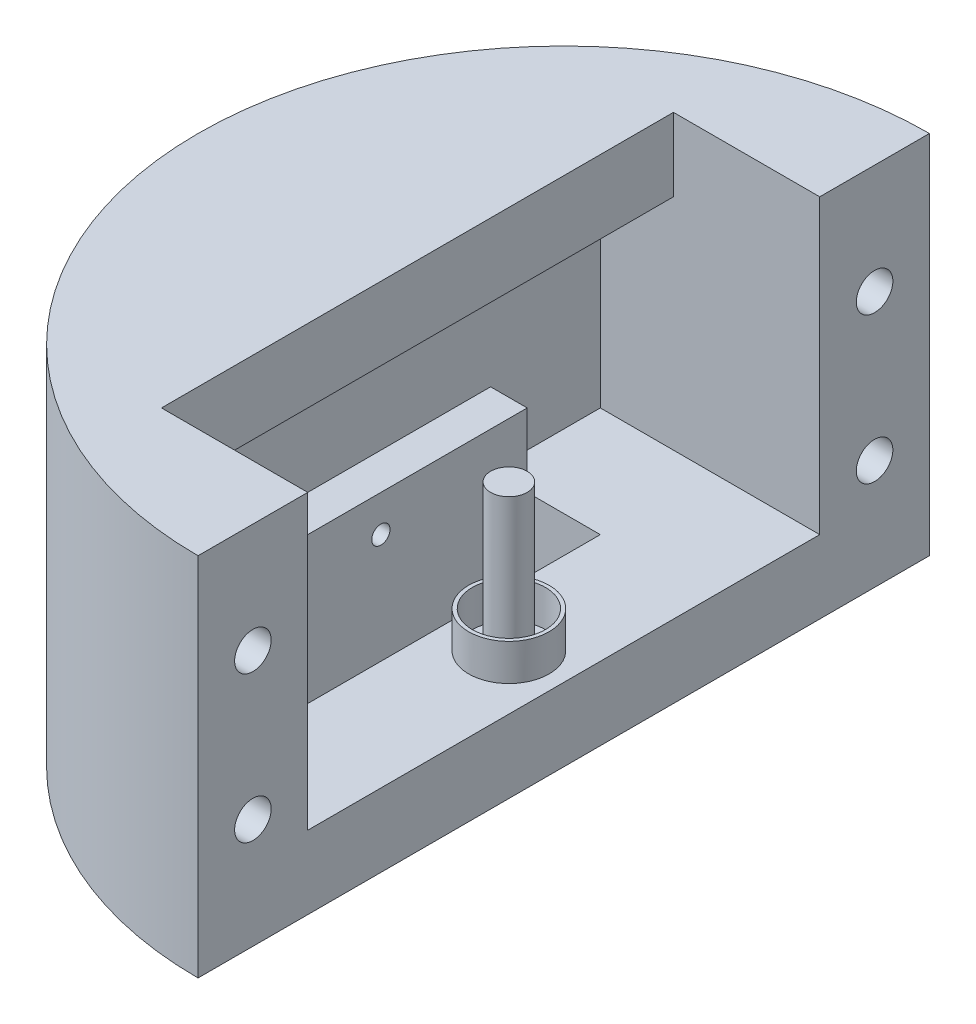
SolidWorks part; units mm, degrees
material "PP Kopolimer"
ref_plane "Front Plane" through (0, 0, 0) normal (0, 0, 1) x (1, 0, 0)
ref_plane "Top Plane" through (0, 0, 0) normal (0, 1, 0) x (1, 0, 0)
ref_plane "Right Plane" through (0, 0, 0) normal (1, 0, 0) x (0, 0, -1)
sketch "Szkic1" plane through (0, 0, 0) normal (0, 1, 0) x (1, 0, 0)
  line L1 (-2.5, -5) -> (2.5, -5)
  line L2 (-2.5, -5) -> (-2.5, 5)
  line L3 (-2.5, 5) -> (2.5, 5)
  line L4 (2.5, -5) -> (2.5, 5)
  line L5 (-2.5, -5) -> (2.5, 5) construction
  line L6 (-2.5, 5) -> (2.5, -5) construction
  point P0 (0, 0)
extrude "Dodanie-wyciągnięcie1" add sketch "Szkic1" along normal blind 1
sketch "Szkic2" plane through (0, 1, 0) normal (0, 1, 0) x (1, 0, 0)
  line L0 (2.5, -5) -> (2.5, 5) construction
  line L1 (-2.5, 5) -> (2.5, 5)
  line L10 (-2.5, 5) -> (-2.5, -5)
  line L15 (-2.5, -5) -> (2.5, -5)
  line L16 (2.5, 3.5) -> (2.5, 5)
  line L17 (-0.5, 3.5) -> (-0.5, -3.5)
  line L18 (2.5, -3.5) -> (2.5, -5)
  line L19 (2.5, 3.5) -> (-0.5, 3.5)
  line L20 (2.5, -3.5) -> (-0.5, -3.5)
extrude "Dodanie-wyciągnięcie4" add sketch "Szkic2" along normal blind 4 contours L17 L20 L18 L15 L10 L1 L16 L19
fillet "Zaokrąglenie2" radius 5 2 edges at (-2.5, 2.5, -5) (-2.5, 2.5, 5)
sketch "Szkic3" plane through (0, 1, 0) normal (0, 1, 0) x (1, 0, 0)
  line L0 (-0.5, 0) -> (0, 0) construction
  line L1 (-0.5, 3.5) -> (-0.5, -3.5) construction
  line L2 (0, 0) -> (0, 2) construction
  line L4 (0, 2) -> (1, 2)
  line L5 (0, 2) -> (0, -2)
  line L6 (0, -2) -> (1, -2)
  line L7 (1, 2) -> (1, -2)
extrude "Wytnij-wyciągnięcie1" cut sketch "Szkic3" against normal blind 4
sketch "Szkic4" plane through (0, 1, 0) normal (0, 1, 0) x (1, 0, 0)
  line L0 (-0.5, 3.5) -> (-0.5, -3.5) construction
  line L1 (0, 2) -> (-0.5, 2)
  line L2 (0, 2) -> (0, -2)
  line L3 (0, -2) -> (-0.5, -2)
  line L4 (-0.5, 2) -> (-0.5, -2)
extrude "Dodanie-wyciągnięcie5" add sketch "Szkic4" along normal blind 1
sketch "Szkic5" plane through (0, 1, 0) normal (0, 1, 0) x (1, 0, 0)
  line L0 (1, 0) -> (2.5, 0) construction
  line L1 (1, -2) -> (1, 2) construction
  line L2 (2.5, -3.5) -> (2.5, 3.5) construction
  circle A0 centre (1.75, 0) radius 0.25
extrude "Dodanie-wyciągnięcie6" add sketch "Szkic5" along normal blind 2
sketch "Szkic6" plane through (0, 1, 0) normal (0, 1, 0) x (1, 0, 0)
  circle A0 centre (1.75, 0) radius 0.5
  circle A1 centre (1.75, 0) radius 0.55
extrude "Dodanie-wyciągnięcie7" add sketch "Szkic6" along normal blind 0.5
sketch "Szkic7" plane through (-0.5, 0, 0) normal (1, 0, 0) x (0, 0, -1)
  line L0 (-3.5, 5) -> (-3.5, 1) construction
  line L1 (3.5, 5) -> (-3.5, 5)
  line L2 (3.5, 5) -> (3.5, 4)
  line L3 (3.5, 4) -> (-3.5, 4)
  line L4 (-3.5, 5) -> (-3.5, 4)
extrude "Dodanie-wyciągnięcie8" add sketch "Szkic7" along normal blind 1
sketch "Szkic11" plane through (2.5, 0, 0) normal (1, 0, 0) x (0, 0, -1)
  line L0 (-4.25, 5) -> (-4.25, 3.5031)
  line L1 (-3.5, 5) -> (-5, 5) construction
  line L2 (-4.25, 3.5031) -> (-4.25, 1.5031)
  line L3 (4.25, 5) -> (4.25, 3.5031) construction
  line L4 (3.5, 5) -> (5, 5) construction
  line L5 (4.25, 3.5031) -> (4.25, 1.5031) construction
  circle A0 centre (-4.25, 3.5031) radius 0.25
  circle A1 centre (-4.25, 1.5031) radius 0.25
  circle A2 centre (4.25, 3.5031) radius 0.25
  circle A3 centre (4.25, 1.5031) radius 0.25
extrude "Wytnij-wyciągnięcie2" cut sketch "Szkic11" against normal blind 0.5 contours A2 | A3 | A0 | A1 region at (2.5, 3.5031, -4.25)
sketch "Szkic14" plane through (0, 0, 0) normal (1, 0, 0) x (0, 0, -1)
  line L0 (0, 0) -> (0, 1.5) construction
  circle A0 centre (0, 1.5) radius 0.125
extrude "Wytnij-wyciągnięcie3" cut sketch "Szkic14" against normal blind 1
